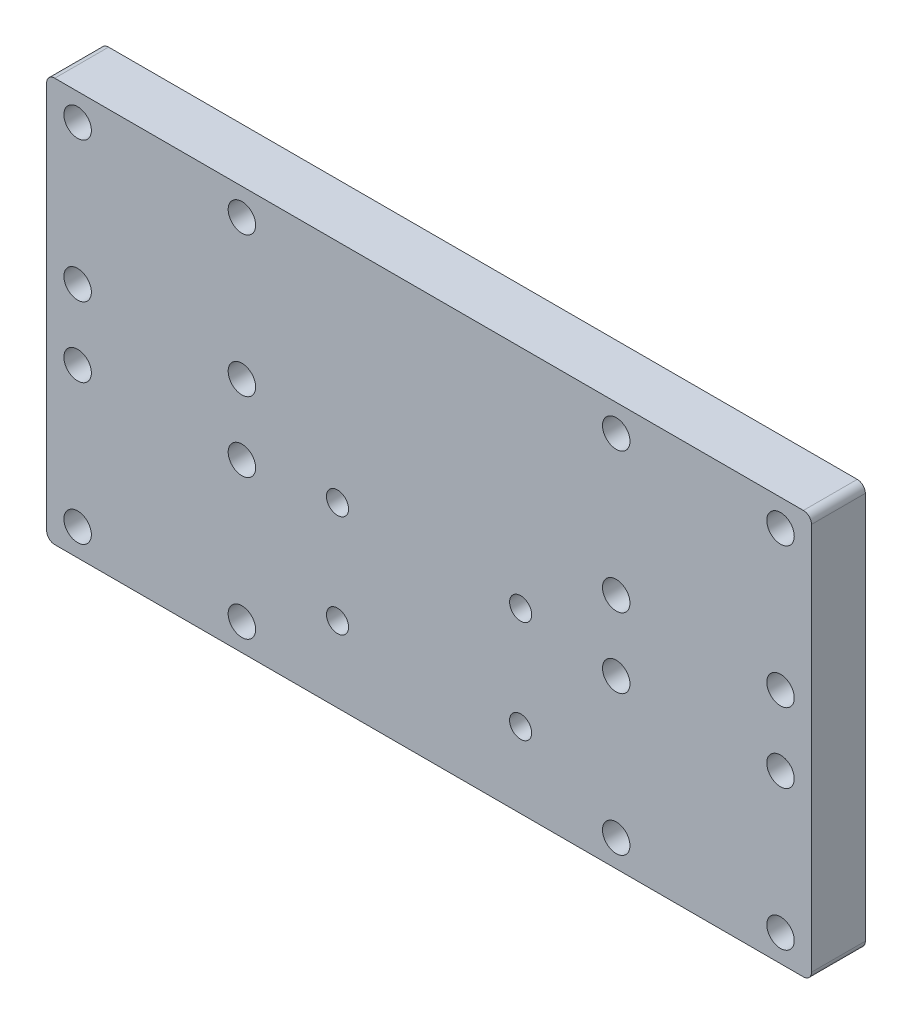
SolidWorks part; units mm, degrees
ref_plane "Front Plane" through (0, 0, 0) normal (0, 0, 1) x (1, 0, 0)
ref_plane "Top Plane" through (0, 0, 0) normal (0, 1, 0) x (1, 0, 0)
ref_plane "Right Plane" through (0, 0, 0) normal (1, 0, 0) x (0, 0, -1)
sketch "Sketch1" plane through (0, 0, 0) normal (0, 0, 1) x (1, 0, 0)
  line L1 (-71, -37.5) -> (71, -37.5)
  line L2 (-71, -37.5) -> (-71, 37.5)
  line L3 (-71, 37.5) -> (71, 37.5)
  line L4 (71, -37.5) -> (71, 37.5)
  line L5 (-71, -37.5) -> (71, 37.5) construction
  line L6 (-71, 37.5) -> (71, -37.5) construction
  point P0 (0, 0)
  dimension "D1" = 75
  dimension "D2" = 142
extrude "Boss-Extrude1" add sketch "Sketch1" along normal mid plane 10
sketch "Sketch2" plane through (0, 0, 5) normal (0, 0, 1) x (1, 0, 0)
  line L3 (-65.25, 37.5) -> (-65.25, -37.5)
  line L4 (-65.25, 37.5) -> (-65.25, -37.5) construction
  line L6 (65.25, -37.5) -> (65.25, 37.5)
  line L7 (65.25, -37.5) -> (65.25, 37.5) construction
  line L13 (-34.75, 37.5) -> (-34.75, -37.5)
  line L14 (-34.75, 37.5) -> (-34.75, -37.5) construction
  line L16 (34.75, -37.5) -> (34.75, 37.5)
  line L18 (34.75, -37.5) -> (34.75, 37.5) construction
  line L20 (71, 32.5) -> (-71, 32.5)
  line L21 (71, 32.5) -> (-71, 32.5) construction
  line L23 (-71, -32.5) -> (71, -32.5)
  line L24 (-71, -32.5) -> (71, -32.5) construction
  line L26 (71, 6.5) -> (-71, 6.5)
  line L27 (71, 6.5) -> (-71, 6.5) construction
  line L29 (-71, -6.5) -> (71, -6.5)
  line L30 (-71, -6.5) -> (71, -6.5) construction
  circle A0 centre (-65.25, 32.5) radius 2.55
  circle A1 centre (-34.75, 32.5) radius 2.55
  circle A2 centre (-34.75, 6.5) radius 2.55
  circle A3 centre (-65.25, 6.5) radius 2.55
  circle A4 centre (65.25, 32.5) radius 2.55
  circle A5 centre (65.25, 6.5) radius 2.55
  circle A6 centre (34.75, 6.5) radius 2.55
  circle A7 centre (34.75, 32.5) radius 2.55
  circle A8 centre (-65.25, -6.5) radius 2.55
  circle A9 centre (-34.75, -6.5) radius 2.55
  circle A10 centre (-34.75, -32.5) radius 2.55
  circle A11 centre (-65.25, -32.5) radius 2.55
  circle A12 centre (34.75, -6.5) radius 2.55
  circle A13 centre (65.25, -6.5) radius 2.55
  circle A14 centre (65.25, -32.5) radius 2.55
  circle A15 centre (34.75, -32.5) radius 2.55
  dimension "D9" = 5.1
  dimension "D10" = 5.1
  dimension "D11" = 5.1
  dimension "D12" = 5.1
  dimension "D13" = 5.1
  dimension "D14" = 5.1
  dimension "D15" = 5.1
  dimension "D16" = 5.1
  dimension "D17" = 5.1
  dimension "D18" = 5.1
  dimension "D19" = 5.1
  dimension "D20" = 5.1
  dimension "D21" = 5.1
  dimension "D22" = 5.1
  dimension "D23" = 5.1
  dimension "D24" = 5.1
  dimension "D1" = 5.75
  dimension "D2" = 5.75
  dimension "D3" = 36.25
  dimension "D4" = 36.25
  dimension "D5" = 5
  dimension "D6" = 5
  dimension "D7" = 31
  dimension "D8" = 31
extrude "Cut-Extrude1" cut sketch "Sketch2" against normal through all
sketch "Sketch3" plane through (0, 0, 5) normal (0, 0, 1) x (1, 0, 0)
  line L0 (-71, -37.5) -> (71, -37.5) construction
  line L1 (-17, -4.5) -> (17, -4.5) construction
  line L2 (-17, -4.5) -> (-17, -23.5) construction
  line L3 (-17, -23.5) -> (17, -23.5) construction
  line L4 (17, -4.5) -> (17, -23.5) construction
  line L5 (-17, -4.5) -> (17, -23.5) construction
  line L6 (-17, -23.5) -> (17, -4.5) construction
  line L7 (0, 37.5) -> (0, -37.5) construction
  line L8 (71, 37.5) -> (-71, 37.5) construction
  circle A0 centre (-17, -4.5) radius 2.05
  circle A1 centre (-17, -23.5) radius 2.05
  circle A2 centre (17, -23.5) radius 2.05
  circle A3 centre (17, -4.5) radius 2.05
  point P0 (0, 0)
  dimension "D3" = 4.1
  dimension "D4" = 4.1
  dimension "D5" = 4.1
  dimension "D6" = 4.1
  dimension "D1" = 34
  dimension "D2" = 19
  dimension "D7" = 14
  dimension "D8" = 17
extrude "Cut-Extrude2" cut sketch "Sketch3" against normal through all
fillet "Fillet1" radius 1.5 4 edges at (-71, -37.5, 0) (71, -37.5, 0) (71, 37.5, 0) (-71, 37.5, 0)
equation "\"D4@Sketch3\"=\"D3@Sketch3\""
equation "\"D5@Sketch3\"=\"D3@Sketch3\""
equation "\"D6@Sketch3\"=\"D3@Sketch3\""
